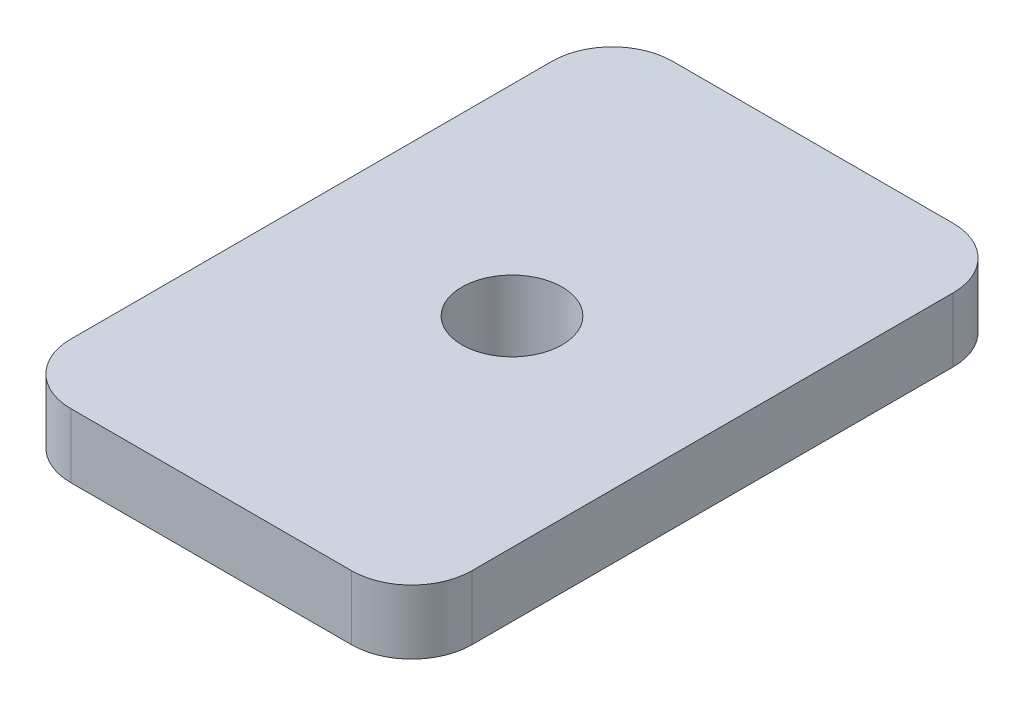
SolidWorks part; units mm, degrees
material "Plain Carbon Steel"
ref_plane "Front" through (0, 0, 0) normal (0, 0, 1) x (1, 0, 0)
ref_plane "Top" through (0, 0, 0) normal (0, 1, 0) x (1, 0, 0)
ref_plane "Right" through (0, 0, 0) normal (1, 0, 0) x (0, 0, -1)
sketch "Sketch1" plane through (0, 0, 0) normal (0, 1, 0) x (1, 0, 0)
  line L1 (0, 0) -> (10, 0)
  line L2 (0, 0) -> (0, 15)
  line L3 (0, 15) -> (10, 15)
  line L4 (10, 0) -> (10, 15)
  dimension "D1" = 15
  dimension "D2" = 10
extrude "Boss-Extrude1" add sketch "Sketch1" along normal blind 1.6
fillet "Fillet1" radius 1.5 4 edges at (0, 0.8, -15) (10, 0.8, -15) (0, 0.8, 0) (10, 0.8, 0)
sketch "Sketch2" plane through (0, 0, 0) normal (0, -1, 0) x (1, 0, 0)
  line L0 (0, -7.5) -> (5, -7.5) construction
  line L1 (0, -13.5) -> (0, -1.5) construction
  line L2 (5, -7.5) -> (5, -15) construction
  line L3 (8.5, -15) -> (1.5, -15) construction
  circle A0 centre (5, -7.5) radius 3.45
  dimension "D1" = 6.9
extrude "Boss-Extrude2" add sketch "Sketch2" along normal blind 1.4
hole_wizard "M3x0.5 Tapped Hole1" positions "Sketch5" profile "Sketch7" tap size "M3x0.5" standard "ANSI Metric" end condition through all
sketch "Sketch5" plane through (0, 1.6, 0) normal (0, 1, 0) x (1, 0, 0)
  point P0 (5, 7.5)
sketch "Sketch7" plane through (5, 1.6, -7.5) normal (1, 0, 0) x (0, 0, 1)
  line L0 (0, 0) -> (0, 3)
  line L1 (0, 3) -> (1.25, 3)
  line L2 (1.25, 3) -> (1.25, 0)
  line L5 (1.25, 0) -> (0, 0)
  line L11 (0, -6.35) -> (0, 107.95) construction
  dimension "Thru Tap Drill Dia." = 2.5
  dimension "Thru Tap Drill Depth" = 3
cosmetic thread "Hole Thread1" parameters "D2"=3
